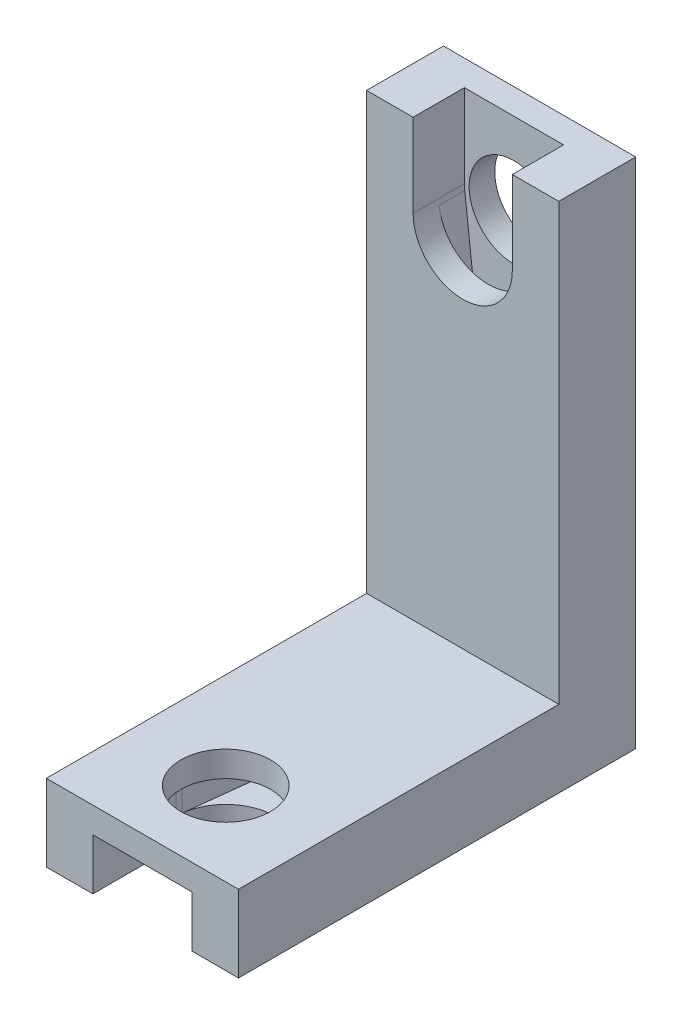
SolidWorks part; units mm, degrees
ref_plane "Front Plane" through (0, 0, 0) normal (0, 0, 1) x (1, 0, 0)
ref_plane "Top Plane" through (0, 0, 0) normal (0, 1, 0) x (1, 0, 0)
ref_plane "Right Plane" through (0, 0, 0) normal (1, 0, 0) x (0, 0, -1)
sketch "Sketch1" plane through (0, 0, 0) normal (1, 0, 0) x (0, 0, -1)
  line L0 (-12.5, -3) -> (-12.5, 3)
  line L1 (-12.5, 3) -> (12.5, 3)
  line L2 (12.5, 3) -> (12.5, 37)
  line L3 (12.5, 37) -> (18.5, 37)
  line L4 (18.5, 37) -> (18.5, -3)
  line L5 (18.5, -3) -> (-12.5, -3)
  line L6 (-12.5, 0) -> (0, 0) construction
  line L7 (0, 0) -> (0, 3) construction
  dimension "D1" = 25
  dimension "D2" = 6
  dimension "D3" = 40
  dimension "D4" = 6
extrude "Boss-Extrude1" add sketch "Sketch1" along normal mid plane 15
sketch "Sketch2" plane through (0, 0, 0) normal (0, 1, 0) x (1, 0, 0)
  line L0 (0, -9.5) -> (0, -12.5) construction
  line L1 (7.5, -12.5) -> (-7.5, -12.5) construction
  circle A0 centre (0, -6) radius 3.5
  dimension "D1" = 7
  dimension "D2" = 3
extrude "Cut-Extrude1" cut sketch "Sketch2" along normal through all
sketch "Sketch3" plane through (0, 0, 0) normal (0, 1, 0) x (1, 0, 0)
  line L0 (3.8443, -5.5547) -> (2.2351, 8.3389)
  line L1 (-2.2351, 8.3389) -> (-3.8443, -5.5547)
  line L2 (3.596, -5.5835) -> (1.9867, 8.3101)
  line L3 (-1.9867, 8.3101) -> (-3.596, -5.5835)
  line L4 (3.596, -5.5835) -> (1.9867, 8.3101) construction
  line L5 (-1.9867, 8.3101) -> (-3.596, -5.5835) construction
  line L6 (3.87, -6) -> (3.87, -12.5)
  line L7 (3.87, -12.5) -> (-3.87, -12.5)
  line L8 (-3.87, -12.5) -> (-3.87, -6)
  line L9 (7.5, -12.5) -> (-7.5, -12.5) construction
  arc A0 (2.2351, 8.3389) -> (-2.2351, 8.3389) centre (0, 8.08) ccw
  arc A1 (-3.8443, -5.5547) -> (-3.87, -6) centre (0, -6) ccw
  arc A2 (1.9867, 8.3101) -> (-1.9867, 8.3101) centre (0, 8.08) ccw
  arc A3 (-3.596, -5.5835) -> (3.596, -5.5835) centre (0, -6) ccw
  arc A4 (1.9867, 8.3101) -> (-1.9867, 8.3101) centre (0, 8.08) ccw construction
  arc A5 (-3.596, -5.5835) -> (3.596, -5.5835) centre (0, -6) ccw construction
  arc A6 (3.87, -6) -> (3.8443, -5.5547) centre (0, -6) ccw
  arc A7 (-3.8443, -5.5547) -> (3.8443, -5.5547) centre (0, -6) ccw construction
  point P16 (0, 0)
  dimension "D1" = 0
  dimension "D2" = 0.25
extrude "Cut-Extrude2" cut sketch "Sketch3" against normal mid plane 2
sketch "Sketch4" plane through (0, 0, 0) normal (0, 1, 0) x (1, 0, 0)
  line L0 (-3.87, -6) -> (-3.87, -12.5) construction
  line L1 (3.87, -12.5) -> (3.87, -6) construction
  line L2 (-3.87, -6) -> (-3.87, -12.5)
  line L3 (3.87, -12.5) -> (3.87, -6)
  line L4 (3.87, -12.5) -> (-3.87, -12.5)
  arc A0 (3.87, -6) -> (-3.87, -6) centre (0, -6) ccw
extrude "Cut-Extrude3" cut sketch "Sketch4" against normal through all
ref_plane "Plane1" through (0, 0, -15.5) normal (0, 0, 1) x (1, 0, 0)
sketch "Sketch6" plane through (0, 0, -15.5) normal (0, 0, 1) x (1, 0, 0)
  line L0 (0, 34) -> (0, 37) construction
  line L2 (7.5, 37) -> (-7.5, 37) construction
  circle A0 centre (0, 30.5) radius 3.5
  point P5 (0, 0)
  point P8 (0, 0)
  dimension "D2" = 7
  dimension "D1" = 3
extrude "Cut-Extrude4" cut sketch "Sketch6" against normal through all
sketch "Sketch7" plane through (0, 0, -15.5) normal (0, 0, 1) x (1, 0, 0)
  line L0 (2.2351, 16.1611) -> (3.8443, 30.0547)
  line L1 (-3.8443, 30.0547) -> (-2.2351, 16.1611)
  line L2 (1.9867, 16.1899) -> (3.596, 30.0835)
  line L3 (-3.596, 30.0835) -> (-1.9867, 16.1899)
  line L4 (1.9867, 16.1899) -> (3.596, 30.0835) construction
  line L5 (-3.596, 30.0835) -> (-1.9867, 16.1899) construction
  line L6 (3.87, 30.5) -> (3.87, 37)
  line L7 (3.87, 37) -> (-3.87, 37)
  line L8 (-3.87, 37) -> (-3.87, 30.5)
  line L9 (7.5, 37) -> (-7.5, 37) construction
  arc A0 (3.8443, 30.0547) -> (3.87, 30.5) centre (0, 30.5) ccw
  arc A1 (-2.2351, 16.1611) -> (2.2351, 16.1611) centre (0, 16.42) ccw
  arc A2 (-1.9867, 16.1899) -> (1.9867, 16.1899) centre (0, 16.42) ccw
  arc A3 (3.596, 30.0835) -> (-3.596, 30.0835) centre (0, 30.5) ccw
  arc A4 (-1.9867, 16.1899) -> (1.9867, 16.1899) centre (0, 16.42) ccw construction
  arc A5 (3.596, 30.0835) -> (-3.596, 30.0835) centre (0, 30.5) ccw construction
  arc A6 (-3.87, 30.5) -> (-3.8443, 30.0547) centre (0, 30.5) ccw
  arc A7 (3.8443, 30.0547) -> (-3.8443, 30.0547) centre (0, 30.5) ccw construction
  point P16 (0, 0)
  point P17 (0, 0)
  dimension "D1" = 0
  dimension "D2" = 0.25
extrude "Cut-Extrude5" cut sketch "Sketch7" against normal mid plane 2
sketch "Sketch8" plane through (0, 0, -16.5) normal (0, 0, 1) x (1, 0, 0)
  line L0 (3.87, 30.5) -> (3.87, 37) construction
  line L1 (-3.87, 37) -> (-3.87, 30.5) construction
  line L2 (3.87, 30.5) -> (3.87, 37)
  line L3 (-3.87, 37) -> (-3.87, 30.5)
  line L4 (-3.87, 37) -> (3.87, 37)
  arc A0 (3.87, 30.5) -> (-3.87, 30.5) centre (0, 30.5) cw
extrude "Cut-Extrude6" cut sketch "Sketch8" along normal through all
